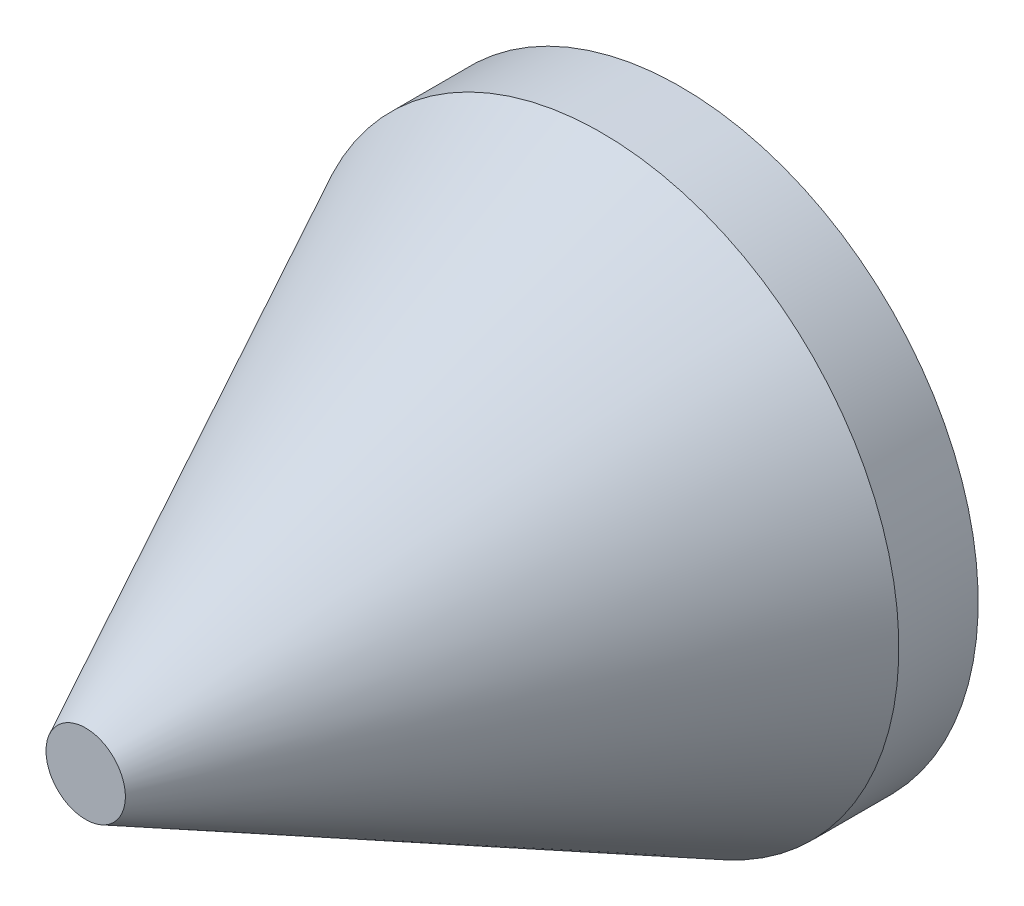
SolidWorks part; units mm, degrees
ref_plane "Front Plane" through (0, 0, 0) normal (0, 0, 1) x (1, 0, 0)
ref_plane "Top Plane" through (0, 0, 0) normal (0, 1, 0) x (1, 0, 0)
ref_plane "Right Plane" through (0, 0, 0) normal (1, 0, 0) x (0, 0, -1)
sketch "Sketch1" plane through (0, 0, 0) normal (0, 1, 0) x (1, 0, 0)
  line L0 (0, 14.5439) -> (0, -58.0895) construction
  line L2 (75, 0) -> (0, 0)
  line L3 (0, 0) -> (0, -150)
  line L4 (75, 0) -> (75, -20)
  line L6 (0, -150) -> (10, -150)
  line L7 (10, -150) -> (75, -20)
  dimension "D1" = 150
  dimension "D2" = 75
  dimension "D3" = 20
  dimension "D4" = 10
revolve "Revolve1" add sketch "Sketch1" angle 360 about L0
equation "\"end_effector_diameter\"=150"
equation "\"D2@Sketch1\"=\"end_effector_diameter\"/2"
equation "\"end_effector_length\"=150"
equation "\"D1@Sketch1\"=\"end_effector_length\""
equation "\"base_link_length\"=150"
equation "\"link1_diameter\"=150"
equation "\"link1_length\"=150"
equation "\"link2_diameter\"=150"
equation "\"link2_length\"=300"
equation "\"link3_diameter\"=150"
equation "\"link3_length\"=150"
equation "\"link4_diameter\"=150"
equation "\"link4_length\"=150"
equation "\"link5_diameter\"=150"
equation "\"link5_length\"=200"
equation "\"base_link_diameterA\"=200"
equation "\"base_link_diameterB\"=150"
equation "\"base_link_lengthA\"=50"
